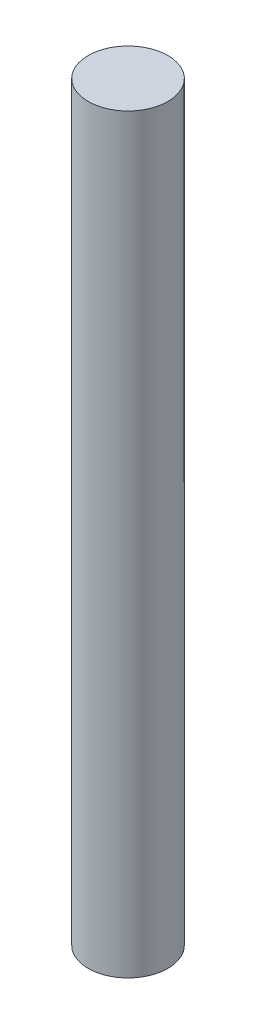
SolidWorks part; units mm, degrees
ref_plane "Front Plane" through (0, 0, 0) normal (0, 0, 1) x (1, 0, 0)
ref_plane "Top Plane" through (0, 0, 0) normal (0, 1, 0) x (1, 0, 0)
ref_plane "Right Plane" through (0, 0, 0) normal (1, 0, 0) x (0, 0, -1)
sketch "Sketch1" plane through (0, 0, 0) normal (0, 1, 0) x (1, 0, 0)
  circle A0 centre (0, 0) radius 1.5
  dimension "D1" = 3
extrude "Boss-Extrude1" add sketch "Sketch1" along normal blind 28.27
